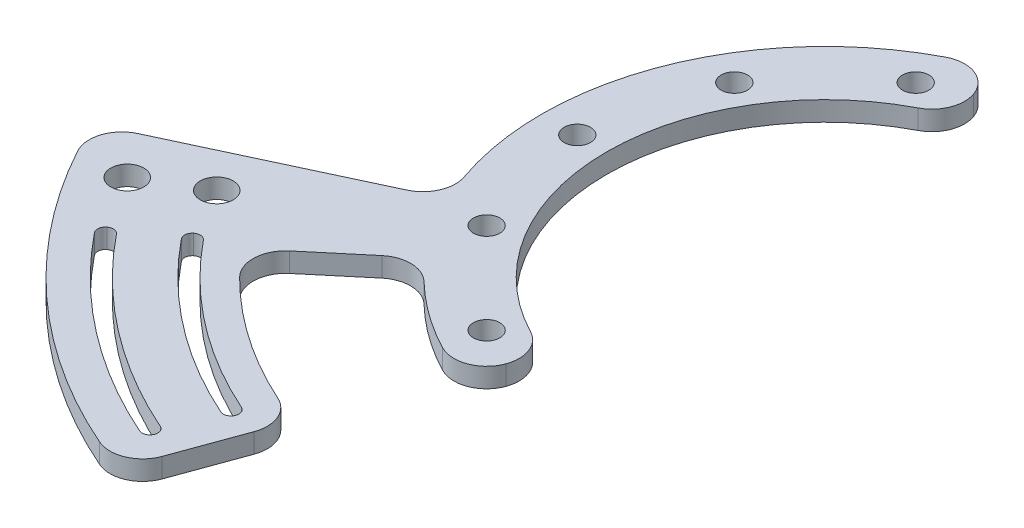
SolidWorks part; units mm, degrees
ref_plane "Front Plane" through (0, 0, 0) normal (0, 0, 1) x (1, 0, 0)
ref_plane "Top Plane" through (0, 0, 0) normal (0, 1, 0) x (1, 0, 0)
ref_plane "Right Plane" through (0, 0, 0) normal (1, 0, 0) x (0, 0, -1)
sketch "Sketch1" plane through (0, 0, 0) normal (0, 1, 0) x (1, 0, 0)
  circle A0 centre (0, 0) radius 38 construction
  circle A1 centre (0, 0) radius 43.5
  circle A2 centre (0, 0) radius 33.5
  dimension "D1" = 76
  dimension "D2" = 67
  dimension "D3" = 87
extrude "Boss-Extrude1" add sketch "Sketch1" along normal blind 3
sketch "Sketch3" plane through (0, 3, 0) normal (0, 1, 0) x (1, 0, 0)
  line L0 (0, 0) -> (-38, 0) construction
  circle A0 centre (-38, 0) radius 2.025
  dimension "D1" = 4.05
  dimension "D2" = 38
extrude "Cut-Extrude2" cut sketch "Sketch3" against normal through all both and the other way through all
pattern_circular "CirPattern1" count 12 over 360 about axis through (0, 3, 0) along (0, 1, 0) of "Cut-Extrude2"
sketch "Sketch2" plane through (0, 3, 0) normal (0, 1, 0) x (1, 0, 0)
  line L0 (0, 0) -> (43.5, 0)
  line L1 (0, 0) -> (-14.8779, -40.8766)
  circle A0 centre (0, 0) radius 43.5 construction
  arc A1 (-14.8779, -40.8766) -> (43.5, 0) centre (0, 0) ccw
  dimension "D1" = 110
extrude "Cut-Extrude1" cut sketch "Sketch2" against normal through all both and the other way through all
mirror "Mirror1" about plane through (0, 0, 0) normal (0, 0, 1) of "Cut-Extrude1"
sketch "Sketch4" plane through (0, 0, 0) normal (0, 1, 0) x (1, 0, 0)
  line L0 (0, 0) -> (-43.5, 0) construction
  line L1 (0, 0) -> (-76.583, -35.7112)
  line L2 (-28.9007, -79.404) -> (-21.7183, -59.6705)
  line L3 (-57.5505, -26.8363) -> (-76.583, -35.7112)
  line L4 (-48.6438, -40.817) -> (-33.3229, -27.9613)
  arc A0 (-14.8779, 40.8766) -> (-14.8779, -40.8766) centre (0, 0) ccw construction
  arc A1 (-76.583, -35.7112) -> (-28.9007, -79.404) centre (0, 0) ccw
  arc A2 (-21.7183, -59.6705) -> (-57.5505, -26.8363) centre (0, 0) cw construction
  arc A3 (-21.7183, -59.6705) -> (-48.6438, -40.817) centre (0, 0) cw
  arc A4 (-33.3229, -27.9613) -> (-39.4244, -18.3839) centre (0, 0) cw
  dimension "D5" = 40
  dimension "D1" = 21
  dimension "D2" = 63.5
  dimension "D3" = 25
  dimension "D4" = 70
extrude "Boss-Extrude2" add sketch "Sketch4" along normal up to surface (3 mm away) contours L4 L1 A1 L2 region at (-48.3868, 0, 48.9454) up to face at (-38, 3, 2.025)
sketch "Sketch5" plane through (0, 3, 0) normal (0, 1, 0) x (1, 0, 0)
  line L0 (-30.6724, -72.2596) -> (-26.9604, -63.5148) construction
  line L1 (-61.8588, -48.3294) -> (-54.3727, -42.4806) construction
  line L2 (-28.9007, -79.404) -> (-21.7183, -59.6705) construction
  line L3 (-39.4244, -18.3839) -> (-76.583, -35.7112) construction
  arc A0 (-54.3727, -42.4806) -> (-26.9604, -63.5148) centre (0, 0) ccw
  arc A1 (-61.8588, -48.3294) -> (-30.6724, -72.2596) centre (0, 0) ccw
  arc A2 (-48.6438, -40.817) -> (-21.7183, -59.6705) centre (0, 0) ccw construction
  point P1 (-36.5676, -60.7353)
  point P8 (0, 0)
  point P9 (-64.0647, -31.2466)
  dimension "D4" = 5.5
  dimension "D1" = 9.5
  dimension "D2" = 3
  dimension "D3" = 13
extrude "Cut-Extrude-Thin1" cut sketch "Sketch5" against normal blind 3 thin thin type mid plane wall 2.4
fillet "Fillet1" radius 1.2 8 edges at (-55.3184, 1.5, 43.2194) (-62.8045, 1.5, 49.0682) (-53.4271, 1.5, 41.7418) (-60.9132, 1.5, 47.5906) (-26.4916, 1.5, 62.4102) (-30.2035, 1.5, 71.155) (-27.4293, 1.5, 64.6194) (-31.1413, 1.5, 73.3642)
fillet "Fillet2" radius 5 10 edges at (-11.4577, 1.5, -31.4797) (-11.4577, 1.5, 31.4797) (-39.4244, 1.5, 18.3839) (-76.583, 1.5, 35.7112) (-28.9007, 1.5, 79.404) (-21.7183, 1.5, 59.6705) (-33.3229, 1.5, 27.9613) (-48.6438, 1.5, 40.817)
sketch "Sketch6" plane through (0, 3, 0) normal (0, 1, 0) x (1, 0, 0)
  line L0 (0, 0) -> (-72.4306, -43.5207) construction
  line L1 (-43.7217, -20.3878) -> (-71.9088, -33.5316) construction
  arc A0 (-74.1854, -40.4571) -> (-33.8375, -77.4292) centre (0, 0) ccw construction
  circle A1 centre (-58.2874, -35.0226) radius 2.525
  circle A2 centre (-66.859, -40.173) radius 2.525
  dimension "D1" = 5.05
  dimension "D2" = 10
  dimension "D3" = 78
  dimension "D4" = 6
extrude "Cut-Extrude3" cut sketch "Sketch6" against normal through all both and the other way through all
